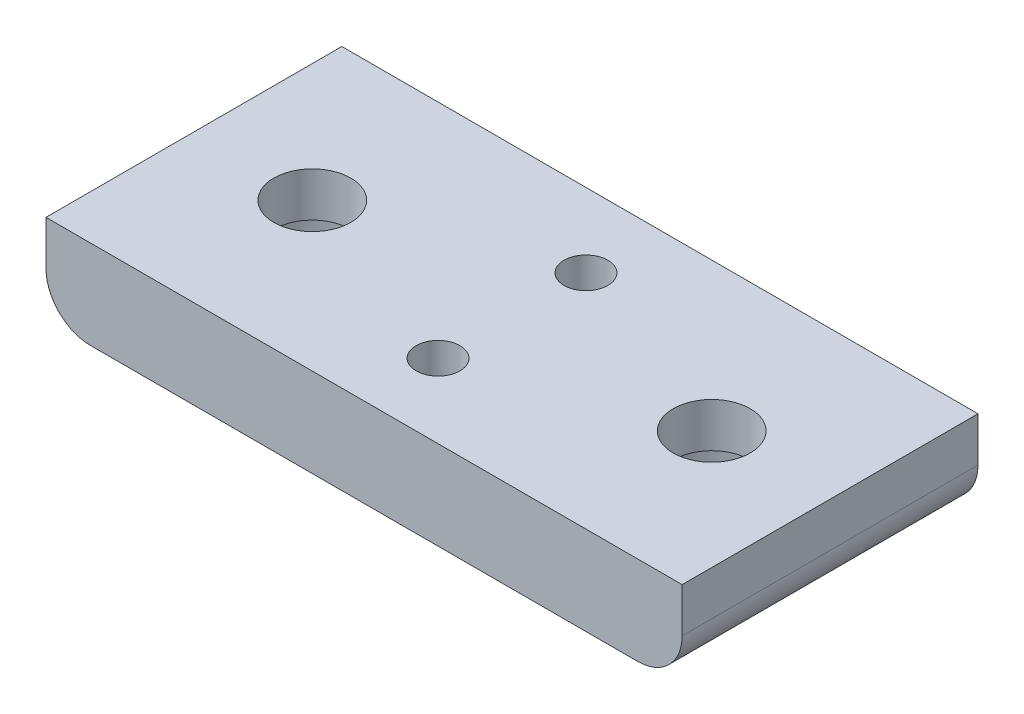
SolidWorks part; units mm, degrees
ref_plane "前视基准面" through (0, 0, 0) normal (0, 0, 1) x (1, 0, 0)
ref_plane "上视基准面" through (0, 0, 0) normal (0, 1, 0) x (1, 0, 0)
ref_plane "右视基准面" through (0, 0, 0) normal (1, 0, 0) x (0, 0, -1)
other "Configuration Table"
sketch "草图1" plane through (0, 0, 0) normal (0, 1, 0) x (1, 0, 0)
  line L1 (0, 0) -> (43, 0)
  line L2 (0, 0) -> (0, 20)
  line L3 (0, 20) -> (43, 20)
  line L4 (43, 0) -> (43, 20)
  circle A0 centre (8, 10) radius 5
  circle A1 centre (35, 10) radius 5
  circle A2 centre (21.5, 15) radius 1.48
  circle A3 centre (21.5, 5) radius 1.48
extrude "凸台-拉伸1" add sketch "草图1" along normal blind 6
sketch "草图2" plane through (0, 6, 0) normal (0, 1, 0) x (1, 0, 0)
  circle A0 centre (8, 10) radius 5
  circle A1 centre (8, 10) radius 2.6
  circle A2 centre (35, 10) radius 5
  circle A3 centre (35, 10) radius 2.6
extrude "凸台-拉伸2" add sketch "草图2" against normal blind 3
fillet "圆角1" radius 3 2 edges at (0, 0, -10) (43, 0, -10)
